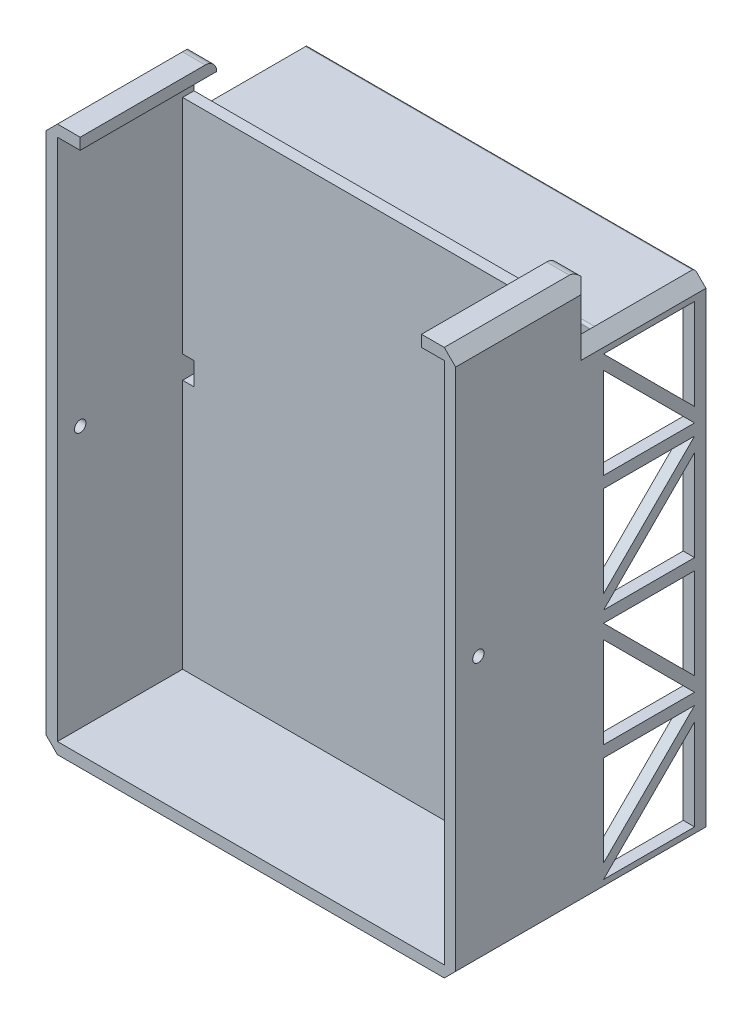
SolidWorks part; units mm, degrees
ref_plane "Front Plane" through (0, 0, 0) normal (0, 0, 1) x (1, 0, 0)
ref_plane "Top Plane" through (0, 0, 0) normal (0, 1, 0) x (1, 0, 0)
ref_plane "Right Plane" through (0, 0, 0) normal (1, 0, 0) x (0, 0, -1)
sketch "Sketch2" plane through (0, 0, 0) normal (0, 1, 0) x (1, 0, 0)
  line L1 (-319.182, -5.0217) -> (40.818, -5.0217)
  line L2 (-319.182, -5.0217) -> (-319.182, -225.0217)
  line L3 (-319.182, -225.0217) -> (40.818, -225.0217)
  line L4 (40.818, -5.0217) -> (40.818, -225.0217)
  point P4 (40.818, -115.0217)
  dimension "D1" = 360
  dimension "D2" = 220
extrude "Boss-Extrude1" add sketch "Sketch2" along normal blind 480
sketch "Sketch4" plane through (0, 480, 0) normal (0, 1, 0) x (1, 0, 0)
  line L0 (-319.182, -225.0217) -> (40.818, -225.0217) construction
  line L9 (-319.182, -5.0217) -> (-319.182, -225.0217) construction
  line L11 (-269.182, -225.0217) -> (-269.182, -115.0217)
  line L12 (-269.182, -115.0217) -> (10.818, -115.0217)
  line L13 (10.818, -225.0217) -> (10.818, -115.0217)
  line L14 (40.818, -5.0217) -> (-319.182, -5.0217) construction
  line L15 (40.818, -225.0217) -> (40.818, -5.0217) construction
  line L17 (-269.182, -225.0217) -> (10.818, -225.0217)
  dimension "D1" = 50
  dimension "D2" = 110
  dimension "D3" = 30
extrude "Cut-Extrude2" cut sketch "Sketch4" against normal blind 470
sketch "Sketch5" plane through (-269.182, 0, 0) normal (1, 0, 0) x (0, 0, -1)
  line L0 (-225.0217, 10) -> (-225.0217, 480) construction
  line L1 (-225.0217, 470) -> (-115.0217, 470)
  line L2 (-225.0217, 470) -> (-225.0217, 10)
  line L3 (-225.0217, 10) -> (-115.0217, 10)
  line L4 (-115.0217, 470) -> (-115.0217, 10)
  line L5 (-115.0217, 480) -> (-225.0217, 480) construction
  line L6 (-115.0217, 10) -> (-115.0217, 480) construction
  line L7 (-115.0217, 10) -> (-225.0217, 10) construction
  dimension "D1" = 10
  dimension "D2" = 0
  dimension "D3" = 0
extrude "Cut-Extrude3" cut sketch "Sketch5" against normal blind 40
sketch "Sketch6" plane through (0, 480, 0) normal (0, 1, 0) x (1, 0, 0)
  line L0 (40.818, -5.0217) -> (-319.182, -5.0217) construction
  line L1 (-309.182, -5.0217) -> (30.818, -5.0217)
  line L2 (-309.182, -5.0217) -> (-309.182, -105.0217)
  line L3 (-309.182, -105.0217) -> (30.818, -105.0217)
  line L4 (30.818, -5.0217) -> (30.818, -105.0217)
  line L5 (40.818, -225.0217) -> (40.818, -5.0217) construction
  line L6 (-319.182, -5.0217) -> (-319.182, -225.0217) construction
  line L7 (10.818, -115.0217) -> (-269.182, -115.0217) construction
  point P8 (-309.182, -55.0217)
  dimension "D1" = 10
  dimension "D2" = 10
  dimension "D3" = 10
extrude "Cut-Extrude4" cut sketch "Sketch6" against normal blind 50 contours L2 L1 L4 L3
sketch "Sketch7" plane through (0, 430, 0) normal (0, 1, 0) x (1, 0, 0)
  line L0 (30.818, -5.0217) -> (30.818, -105.0217) construction
  line L1 (-309.182, -105.0217) -> (30.818, -105.0217)
  line L2 (-309.182, -105.0217) -> (-309.182, -95.0217)
  line L3 (-309.182, -95.0217) -> (30.818, -95.0217)
  line L4 (30.818, -105.0217) -> (30.818, -95.0217)
  dimension "D1" = 10
extrude "Cut-Extrude5" cut sketch "Sketch7" against normal blind 420
sketch "Sketch8" plane through (0, 0, 5.0217) normal (0, 0, -1) x (-1, 0, 0)
  line L0 (-40.818, 0) -> (319.182, 0) construction
  line L1 (309.182, 10) -> (-30.818, 10)
  line L2 (309.182, 10) -> (309.182, 420)
  line L3 (309.182, 420) -> (-30.818, 420)
  line L4 (-30.818, 10) -> (-30.818, 420)
  line L5 (-40.818, 480) -> (-40.818, 0) construction
  line L6 (319.182, 480) -> (319.182, 0) construction
  line L7 (309.182, 430) -> (-30.818, 430) construction
  dimension "D1" = 10
  dimension "D2" = 10
  dimension "D3" = 10
  dimension "D4" = 10
extrude "Cut-Extrude6" cut sketch "Sketch8" against normal blind 90 contours L2 L1 L4 L3
sketch "Sketch12" plane through (0, 0, 105.0217) normal (0, 0, -1) x (-1, 0, 0)
  line L0 (-30.818, 10) -> (-30.818, 480) construction
  line L5 (-30.818, 230) -> (-20.818, 230)
  line L6 (-30.818, 230) -> (-30.818, 250)
  line L7 (-30.818, 250) -> (-20.818, 250)
  line L8 (-20.818, 230) -> (-20.818, 250)
  line L9 (309.182, 10) -> (-30.818, 10) construction
  line L10 (309.182, 480) -> (-30.818, 480) construction
  line L11 (309.182, 10) -> (309.182, 420) construction
  line L16 (309.182, 230) -> (299.182, 230)
  line L17 (309.182, 230) -> (309.182, 250)
  line L18 (309.182, 250) -> (299.182, 250)
  line L19 (299.182, 230) -> (299.182, 250)
  point P6 (-25.818, 230)
  point P9 (-25.818, 250)
  point P18 (304.182, 250)
  dimension "D1" = 10
  dimension "D2" = 220
  dimension "D3" = 230
  dimension "D4" = 0
  dimension "D5" = 20
  dimension "D6" = 230
  dimension "D7" = 10
extrude "Cut-Extrude9" cut sketch "Sketch12" against normal blind 10
sketch "Sketch14" plane through (0, 430, 0) normal (0, 1, 0) x (1, 0, 0)
sketch "Sketch18" plane through (-309.182, 0, 0) normal (1, 0, 0) x (0, 0, -1)
  line L0 (-105.0217, 250) -> (-105.0217, 480) construction
  line L1 (-5.0217, 480) -> (-105.0217, 480)
  line L2 (-5.0217, 480) -> (-5.0217, 430)
  line L3 (-5.0217, 430) -> (-105.0217, 430)
  line L4 (-105.0217, 480) -> (-105.0217, 430)
  dimension "D1" = 50
extrude "Cut-Extrude11" cut sketch "Sketch18" against normal blind 10 and the other way blind 470
sketch "Sketch23" plane through (10.818, 0, 0) normal (-1, 0, 0) x (0, 0, 1)
  line L0 (225.0217, 10) -> (225.0217, 480) construction
  line L1 (115.0217, 10) -> (225.0217, 10)
  line L2 (115.0217, 10) -> (115.0217, 470)
  line L3 (115.0217, 470) -> (225.0217, 470)
  line L4 (225.0217, 10) -> (225.0217, 470)
  line L5 (225.0217, 480) -> (115.0217, 480) construction
  dimension "D1" = 10
extrude "Cut-Extrude13" cut sketch "Sketch23" against normal blind 20
sketch "Sketch24" plane through (0, 480, 0) normal (0, 1, 0) x (1, 0, 0)
  line L0 (-319.182, -225.0217) -> (-269.182, -225.0217) construction
  line L1 (-269.182, -115.0217) -> (-289.182, -115.0217)
  line L2 (-269.182, -115.0217) -> (-269.182, -225.0217)
  line L3 (-269.182, -225.0217) -> (-289.182, -225.0217)
  line L4 (-289.182, -115.0217) -> (-289.182, -225.0217)
  dimension "D1" = 20
extrude "Cut-Extrude14" cut sketch "Sketch24" against normal blind 10
sketch "Sketch20" plane through (40.818, 0, 0) normal (1, 0, 0) x (0, 0, -1)
sketch "Sketch22" plane through (40.818, 0, 0) normal (1, 0, 0) x (0, 0, -1)
sketch "Sketch26" plane through (40.818, 0, 0) normal (1, 0, 0) x (0, 0, -1)
  line L0 (-205.0217, 480) -> (-205.0217, 0) construction
  line L1 (-225.0217, 480) -> (-105.0217, 480) construction
  line L2 (-225.0217, 0) -> (-5.0217, 0) construction
  line L3 (-225.0217, 480) -> (-225.0217, 0) construction
  circle A0 centre (-205.0217, 240) radius 5
  dimension "D2" = 10
  dimension "D1" = 20
extrude "Cut-Extrude15" cut sketch "Sketch26" against normal blind 480
sketch "Sketch27" plane through (40.818, 0, 0) normal (1, 0, 0) x (0, 0, -1)
  line L0 (-105.0217, 430) -> (-5.0217, 430) construction
  line L1 (-5.0217, 430) -> (-5.0217, 0) construction
  line B0 (-15.0217, 220) -> (-15.0217, 300)
  line B1 (-15.0217, 15) -> (-15.0217, 95)
  line B2 (-95.0217, 27.5) -> (-95.0217, 107.5)
  line B3 (-15.0217, 312.5) -> (-15.0217, 315)
  line B4 (-95.0217, 117.5) -> (-95.0217, 197.5)
  line B5 (-95.0217, 232.5) -> (-95.0217, 312.5) construction
  line B6 (-95.0217, 322.5) -> (-95.0217, 397.5) construction
  line B7 (-95.0217, 15) -> (-15.0217, 15)
  line B8 (-15.0217, 15) -> (-15.0217, 95)
  line B9 (-15.0217, 95) -> (-95.0217, 15)
  line B10 (-95.0217, 107.5) -> (-15.0217, 107.5)
  line B11 (-15.0217, 107.5) -> (-95.0217, 27.5)
  line B12 (-95.0217, 27.5) -> (-95.0217, 107.5)
  line B13 (-15.0217, 15) -> (-15.0217, 95)
  line B14 (-15.0217, 210) -> (-15.0217, 130)
  line B15 (-95.0217, 210) -> (-15.0217, 210)
  line B16 (-15.0217, 130) -> (-95.0217, 210)
  line B17 (-15.0217, 117.5) -> (-95.0217, 197.5)
  line B18 (-95.0217, 117.5) -> (-15.0217, 117.5)
  line B19 (-95.0217, 197.5) -> (-95.0217, 117.5)
  line B20 (-15.0217, 415) -> (-15.0217, 335)
  line B21 (-95.0217, 415) -> (-15.0217, 415)
  line B22 (-15.0217, 335) -> (-95.0217, 415)
  line B23 (-15.0217, 322.5) -> (-95.0217, 402.5)
  line B24 (-95.0217, 322.5) -> (-15.0217, 322.5)
  line B25 (-95.0217, 402.5) -> (-95.0217, 322.5)
  line B26 (-95.0217, 220) -> (-15.0217, 220)
  line B27 (-15.0217, 300) -> (-95.0217, 220)
  line B28 (-15.0217, 220) -> (-15.0217, 300)
  line B29 (-95.0217, 312.5) -> (-15.0217, 312.5)
  line B30 (-95.0217, 232.5) -> (-95.0217, 312.5)
  line B31 (-15.0217, 312.5) -> (-95.0217, 232.5)
  line B32 (-15.0217, 130) -> (-15.0217, 210)
  line B33 (-95.0217, 107.5) -> (-95.0217, 27.5) construction
  line B34 (-15.0217, 335) -> (-15.0217, 397.5)
  line B35 (-95.0217, 197.5) -> (-95.0217, 117.5) construction
  line B36 (-95.0217, 232.5) -> (-95.0217, 312.5)
  line B37 (-95.0217, 322.5) -> (-95.0217, 397.5)
  line B38 (-55.0217, 443.5571) -> (-55.0217, -13.5571) construction
  dimension "D1" = 15
  dimension "D2" = 10
sketch_block_instance "Block2-1"
sketch_block "Block2" parameters "D1"=45
extrude "Cut-Extrude16" cut sketch "Sketch27" against normal blind 480 contours B22 B20 B21 | B23 B25 B24 | B31 B29 B30 | B0 B27 B26 | B16 B14 B15 | B4 B18 B17 | B11 B10 B2 | B1 B9 B7 region at (40.818, 246.6667, 41.6884) region at (40.818, 41.6667, 41.6884) region at (40.818, 80.8333, 68.3551) region at (40.818, 144.1667, 68.3551) region at (40.818, 183.3333, 41.6884) region at (40.818, 388.3333, 41.6884) region at (40.818, 349.1667, 68.3551) region at (40.818, 285.8333, 68.3551)
sketch "Sketch28" plane through (0, 0, 5.0217) normal (0, 0, -1) x (-1, 0, 0)
  line L0 (-40.818, 0) -> (319.182, 0) construction
  line L1 (309.182, 10) -> (-30.818, 10)
  line L2 (309.182, 10) -> (309.182, 0)
  line L3 (309.182, 0) -> (-30.818, 0)
  line L4 (-30.818, 10) -> (-30.818, 0)
  line L5 (-40.818, 430) -> (-40.818, 0) construction
  dimension "D1" = 10
extrude "Cut-Extrude17" cut sketch "Sketch28" against normal blind 100
chamfer "Chamfer1" distance 10 angle 45 2 edges at (40.818, 430, 55.0217) (-319.182, 430, 55.0217)
chamfer "Chamfer2" distance 10 angle 45 2 edges at (40.818, 480, 165.0217) (-319.182, 480, 165.0217)
fillet "Fillet2" radius 10 1 edges at (-139.182, 480, 105.0217)
chamfer "Chamfer3" distance 10 angle 45 2 edges at (-319.182, 445, 105.0217) (40.818, 445, 105.0217)
fillet "Fillet4" radius 2 7 edges at (30.818, 0, 55.0217) (-139.182, 0, 105.0217) (-309.182, 0, 55.0217) (30.818, 210, 5.0217) (-309.182, 210, 5.0217) (-139.182, 420, 5.0217) (-139.182, 430, 5.0217)
fillet "Fillet5" radius 2 1 edges at (-139.182, 430, 95.0217)
chamfer "Chamfer4" distance 10 angle 45 2 edges at (-319.182, 0, 115.0217) (40.818, 0, 115.0217)
sketch "Sketch29" plane through (0, 0, 105.0217) normal (0, 0, -1) x (-1, 0, 0)
  line L0 (-30.818, 470) -> (-30.818, 430) construction
  line L1 (309.182, 470) -> (-30.818, 470)
  line L2 (309.182, 470) -> (309.182, 445.2986)
  line L3 (309.182, 445.2986) -> (-30.818, 445.2986)
  line L4 (-30.818, 470) -> (-30.818, 445.2986)
extrude "Cut-Extrude18" cut sketch "Sketch29" against normal blind 10
sketch "Sketch30" plane through (0, 480, 0) normal (0, 1, 0) x (1, 0, 0)
  line L1 (-289.182, -115.0217) -> (10.818, -115.0217)
  line L2 (-289.182, -115.0217) -> (-289.182, -87.4505)
  line L3 (-289.182, -87.4505) -> (10.818, -87.4505)
  line L4 (10.818, -115.0217) -> (10.818, -87.4505)
extrude "Cut-Extrude19" cut sketch "Sketch30" against normal blind 10
